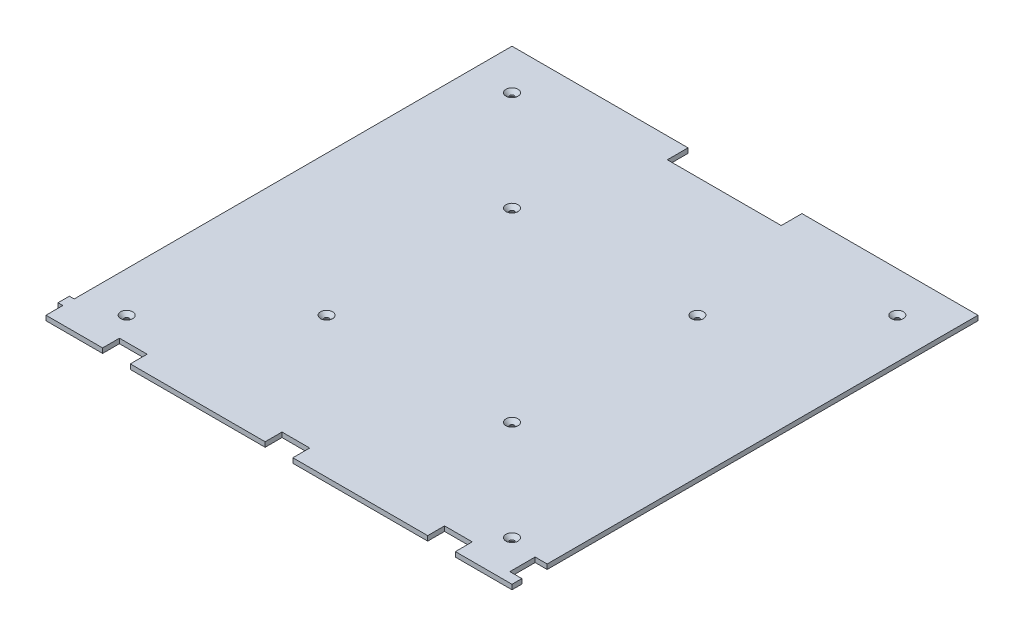
SolidWorks part; units mm, degrees
ref_plane "Front Plane" through (0, 0, 0) normal (0, 0, 1) x (1, 0, 0)
ref_plane "Top Plane" through (0, 0, 0) normal (0, 1, 0) x (1, 0, 0)
ref_plane "Right Plane" through (0, 0, 0) normal (1, 0, 0) x (0, 0, -1)
sketch "Sketch1" plane through (0, 0, 0) normal (0, 1, 0) x (1, 0, 0)
  line L0 (5.5, -97) -> (61.9965, -97) construction
  line L1 (5.5, -90.0036) -> (5.5, -97) construction
  line L2 (-5.5, -90.0036) -> (5.5, -90.0036) construction
  line L3 (-5.5, -97) -> (-5.5, -90.0036) construction
  line L4 (-61.9965, -97) -> (-5.5, -97) construction
  line L5 (-61.9965, -90.0036) -> (-61.9965, -97) construction
  line L6 (-72.9965, -90.0036) -> (-61.9965, -90.0036) construction
  line L7 (-72.9965, -97) -> (-72.9965, -90.0036) construction
  line L8 (-97, -97) -> (-72.9965, -97) construction
  line L9 (-97, -90) -> (-97, -97) construction
  line L10 (-99, -90) -> (-97, -90) construction
  line L11 (-99, -84.8) -> (-99, -90) construction
  line L12 (-97, -84.8) -> (-99, -84.8) construction
  line L13 (-97, 97) -> (-97, -84.8) construction
  line L14 (-23.4, 97) -> (-97, 97) construction
  line L15 (-23.4, 88.4) -> (-23.4, 97) construction
  line L16 (23.4, 88.4) -> (-23.4, 88.4) construction
  line L17 (23.4, 97) -> (23.4, 88.4) construction
  line L18 (97, 97) -> (23.4, 97) construction
  line L19 (97, -82.4) -> (97, 97) construction
  line L20 (92, -82.4) -> (97, -82.4) construction
  line L21 (92, -92.4) -> (92, -82.4) construction
  line L22 (97, -92.4) -> (92, -92.4) construction
  line L23 (97, -97) -> (97, -92.4) construction
  line L24 (72.9965, -97) -> (97, -97) construction
  line L25 (72.9965, -90.0036) -> (72.9965, -97) construction
  line L26 (61.9965, -90.0036) -> (72.9965, -90.0036) construction
  line L27 (61.9965, -97) -> (61.9965, -90.0036) construction
  line L28 (5.75, -96.75) -> (61.7465, -96.75)
  line L29 (61.7465, -96.75) -> (61.7465, -89.7536)
  line L30 (61.7465, -89.7536) -> (73.2465, -89.7536)
  line L31 (73.2465, -89.7536) -> (73.2465, -96.75)
  line L32 (73.2465, -96.75) -> (96.75, -96.75)
  line L33 (96.75, -96.75) -> (96.75, -92.65)
  line L34 (96.75, -92.65) -> (91.75, -92.65)
  line L35 (91.75, -92.65) -> (91.75, -82.15)
  line L36 (91.75, -82.15) -> (96.75, -82.15)
  line L37 (96.75, -82.15) -> (96.75, 96.75)
  line L38 (96.75, 96.75) -> (23.65, 96.75)
  line L39 (23.65, 96.75) -> (23.65, 88.15)
  line L40 (23.65, 88.15) -> (-23.65, 88.15)
  line L41 (-23.65, 88.15) -> (-23.65, 96.75)
  line L42 (-23.65, 96.75) -> (-96.75, 96.75)
  line L43 (-96.75, 96.75) -> (-96.75, -85.05)
  line L44 (-96.75, -85.05) -> (-98.75, -85.05)
  line L45 (-98.75, -85.05) -> (-98.75, -89.75)
  line L46 (-98.75, -89.75) -> (-96.75, -89.75)
  line L47 (-96.75, -89.75) -> (-96.75, -96.75)
  line L48 (-96.75, -96.75) -> (-73.2465, -96.75)
  line L49 (-73.2465, -96.75) -> (-73.2465, -89.7536)
  line L50 (-73.2465, -89.7536) -> (-61.7465, -89.7536)
  line L51 (-61.7465, -89.7536) -> (-61.7465, -96.75)
  line L52 (-61.7465, -96.75) -> (-5.75, -96.75)
  line L53 (-5.75, -96.75) -> (-5.75, -89.7536)
  line L54 (-5.75, -89.7536) -> (5.75, -89.7536)
  line L55 (5.75, -89.7536) -> (5.75, -96.75)
  dimension "D1" = 194
  dimension "D2" = 8.6
  dimension "D3" = 194
  dimension "D4" = 73.6
  dimension "D5" = 46.8
  dimension "D6" = 5
  dimension "D7" = 4.6
  dimension "D8" = 10
  dimension "D9" = 6.9964
  dimension "D10" = 24.0035
  dimension "D11" = 11
  dimension "D12" = 56.4965
  dimension "D13" = 56.4965
  dimension "D14" = 7
  dimension "D15" = 2
  dimension "D16" = 5.2
  dimension "D17" = 97
  dimension "D18" = 97
  dimension "D19" = 0.25
extrude "Boss-Extrude1" add sketch "Sketch1" along normal blind 2
sketch "Sketch2" plane through (0, 0, 0) normal (0, -1, 0) x (1, 0, 0)
  circle A0 centre (80, 80) radius 1
  circle A1 centre (-80, 80) radius 1
  circle A2 centre (-38.5, 38.5) radius 1
  circle A3 centre (38.5, 38.5) radius 1
  circle A4 centre (80, -80) radius 1
  circle A5 centre (-80, -80) radius 1
  circle A6 centre (38.5, -38.5) radius 1
  circle A7 centre (-38.5, -38.5) radius 1
  dimension "D1" = 2
  dimension "D2" = 2
  dimension "D3" = 2
  dimension "D4" = 2
  dimension "D5" = 2
  dimension "D6" = 2
  dimension "D7" = 2
  dimension "D8" = 2
extrude "Cut-Extrude1" cut sketch "Sketch2" against normal through all both and the other way through all
chamfer "Chamfer1" distance 1.5 angle 45 8 edges at (80, 2, 79) (-80, 2, 79) (38.5, 2, 37.5) (-38.5, 2, 37.5) (-38.5, 2, -39.5) (80, 2, -81) (38.5, 2, -39.5) (-80, 2, -81)
sketch "Sketch3" plane through (0, 0, 0) normal (0, -1, 0) x (1, 0, 0)
  line L0 (-23.65, -96.75) -> (-96.75, -96.75) construction
  line L1 (-43.75, -20.75) -> (-33.75, -20.75)
  line L2 (-43.75, -20.75) -> (-43.75, 20.25)
  line L3 (-43.75, 20.25) -> (-33.75, 20.25)
  line L4 (-33.75, -20.75) -> (-33.75, 20.25)
  line L5 (-96.75, -96.75) -> (-96.75, 85.05) construction
  dimension "D1" = 41
  dimension "D2" = 76
  dimension "D3" = 53
  dimension "D4" = 10
extrude "Cut-Extrude2" cut sketch "Sketch3" against normal blind 1.4
